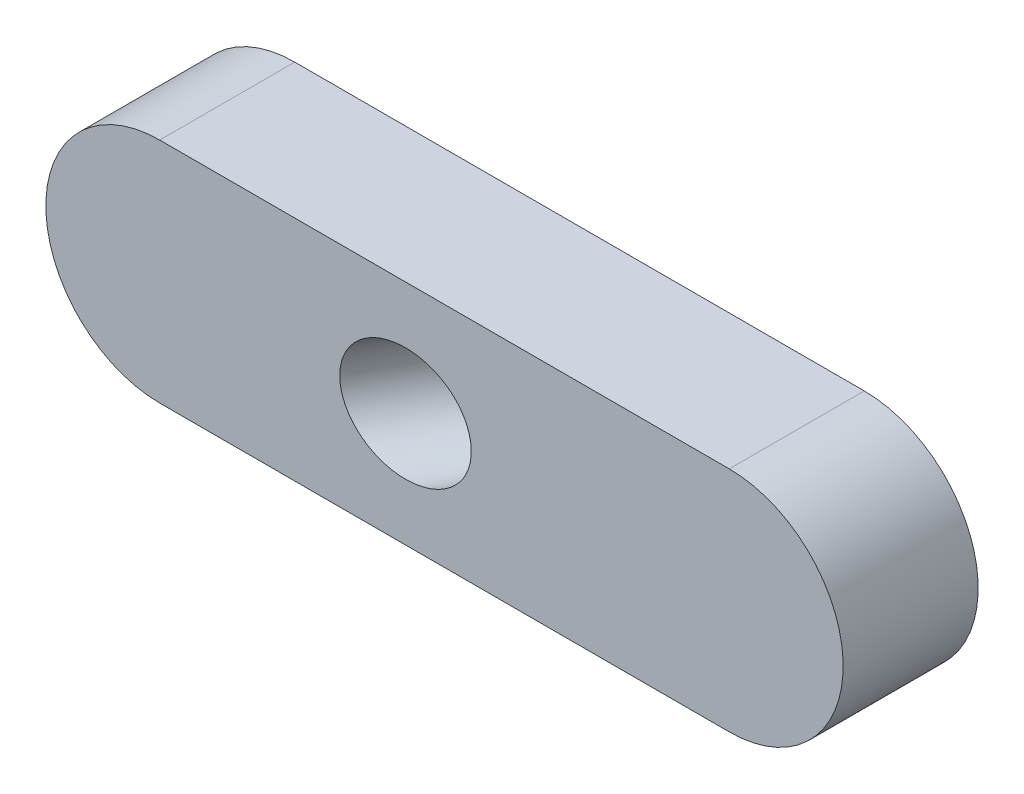
SolidWorks part; units mm, degrees
material "ABS"
ref_plane "Front Plane" through (0, 0, 0) normal (0, 0, 1) x (1, 0, 0)
ref_plane "Top Plane" through (0, 0, 0) normal (0, 1, 0) x (1, 0, 0)
ref_plane "Right Plane" through (0, 0, 0) normal (1, 0, 0) x (0, 0, -1)
ref_axis "Axis1" through (0, -6.6, 0) along (0, 1, 0)
ref_plane "Plane1" through (0, 0, 0) normal (-0.5, 0, 0.866) x (0, 1, 0)
sketch "Sketch1" plane through (0, 0, 0) normal (0, 0, 1) x (1, 0, 0)
  line L0 (-15, 0) -> (15, 0) construction
  line L1 (-15, 6) -> (15, 6)
  line L2 (-15, -6) -> (15, -6)
  arc A0 (-15, 6) -> (-15, -6) centre (-15, 0) ccw
  arc A1 (15, -6) -> (15, 6) centre (15, 0) ccw
  point P0 (0, 0)
  dimension "D1" = 6
  dimension "D2" = 30
extrude "Boss-Extrude1" add sketch "Sketch1" along normal mid plane 7.112
sketch "Sketch6" plane through (0, 0, 0) normal (-0.5, 0, 0.866) x (0, 1, 0)
  line L0 (0, 39.6376) -> (0, 30.3902) construction
  line L1 (0, -3.9116) -> (0, 3.9116) construction
  line L2 (20.1696, 0) -> (32.68, 0) construction
  circle A0 centre (0, 0) radius 3
  point P3 (0, 4.6312)
  dimension "D1" = 6
extrude "Cut-Extrude1" cut sketch "Sketch6" against normal through all both and the other way through all
